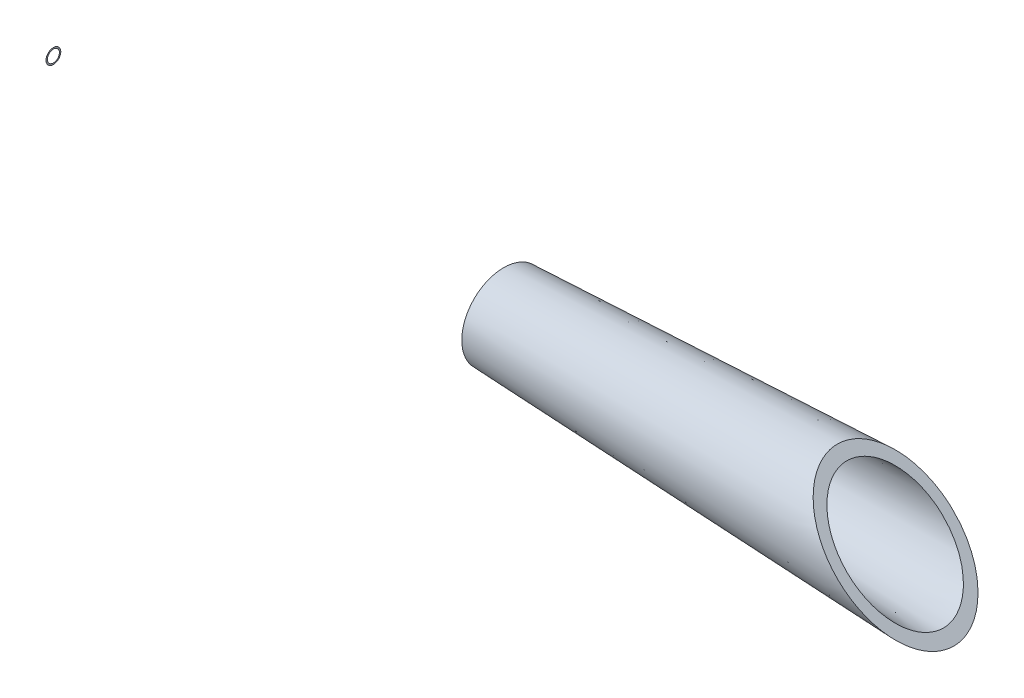
SolidWorks part; units mm, degrees
note: '?' marks a value the reader was unsure of.
ref_plane "Front Plane" through (0, 0, 0) normal (0, 0, 1) x (1, 0, 0)
ref_plane "Top Plane" through (0, 0, 0) normal (0, 1, 0) x (1, 0, 0)
ref_plane "Right Plane" through (0, 0, 0) normal (1, 0, 0) x (0, 0, -1)
sketch "Sketch2" plane through (0, 0, 0) normal (0, 0, 1) x (1, 0, 0)
  line L0 (-19.2758, 0) -> (50, 0) construction
  line L1 (0, 21.4747) -> (0, -15.9358) construction
  line L2 (0, 1.2) -> (54.9325, 5.0413) construction
  line L3 (0, 3.2) -> (55.9028, 7.1091) construction
  line L4 (0, 1.2) -> (50, 4.6963)
  line L5 (1.8511, 3.3294) -> (50, 6.6963)
  line L6 (50, 0) -> (50, 20.2328) construction
  line L7 (50, 6.6963) -> (50, 4.6963)
  arc A0 (0, 1.2) -> (1.8511, 3.3294) centre (1.9903, 1.3392) cw
  dimension "D1" = 4
  dimension "D2" = 1.2
  dimension "D3" = 2
  dimension "D4" = 50
revolve "Revolve2" add sketch "Sketch2" angle 360 about L0
ref_plane "Plane1" through (50, 0, 0) normal (1, 0, 0) x (0, 0, -1)
ref_axis "Axis1" through (50, 0, 0) along (-1, 0, 0)
sketch "Sketch3" plane through (0, 0, 0) normal (0, 0, 1) x (1, 0, 0)
  line L0 (50, 6.6963) -> (180, 6.6963) construction
  line L1 (50, -7.366) -> (50, 7.366) construction
  line L2 (50, 6.6963) -> (1.8511, 3.3294) construction
  line L3 (50, 6.6963) -> (180, 12.145) construction
  line L4 (50, 4.6946) -> (180, 10.1432)
  line L5 (180, 10.1432) -> (180, 12.145)
  line L6 (180, 12.145) -> (50, 6.6963)
  line L7 (50, 6.6963) -> (50, 4.6946)
  dimension "D1" = 2.4
  dimension "D2" = 130
  dimension "D3" = 2
revolve "Revolve3" add sketch "Sketch3" angle 360 about axis through (50, 0, 0) along (-1, 0, 0)
ref_plane "Plane2" through (90, 0, 0) normal (1, 0, 0) x (0, 0, -1)
ref_plane "Plane3" through (180, 0, 0) normal (1, 0, 0) x (0, 0, -1)
ref_plane "Plane4" through (0, -12.145, 0) normal (0, 1, 0) x (1, 0, 0)
ref_axis "Axis2" through (180, -12.145, -13.3595) along (0, 0, 1)?
ref_plane "Plane5" through (83.9275, 83.9275, 0) normal (-0.7071, -0.7071, 0) x (0, 0, 1)
ref_plane "Plane6" through (0, 0, 0) normal (1, 0, 0) x (0, 0, -1)
other "SurfaceCut9" flip cut yes
other "SurfaceCut12"
other "SurfaceCut13"
